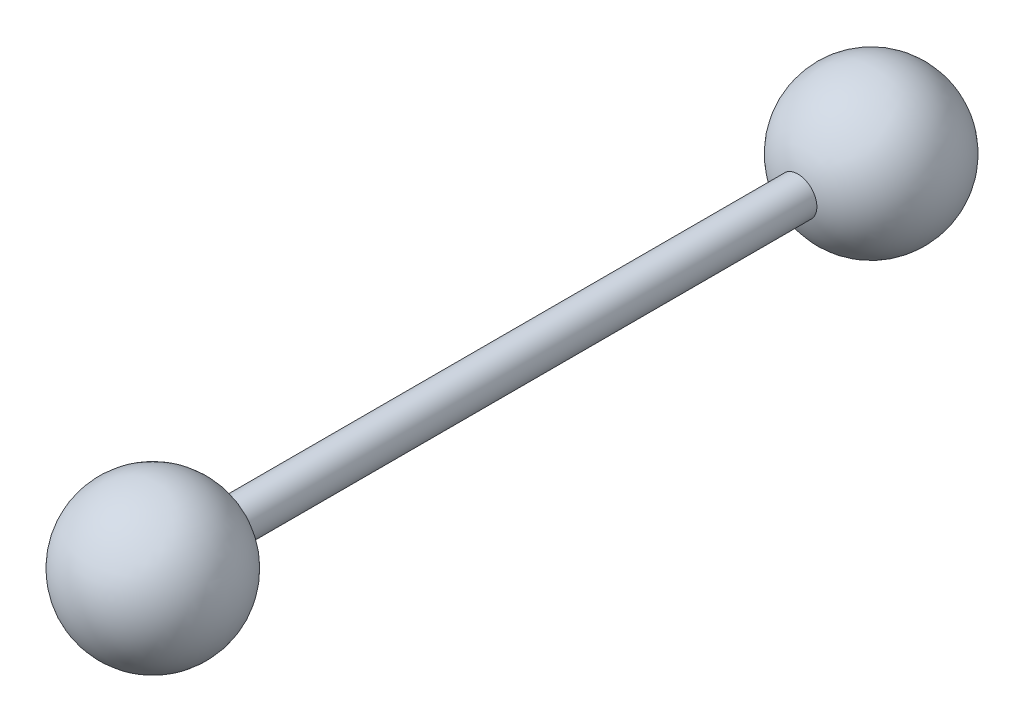
SolidWorks part; units mm, degrees
ref_plane "Front Plane" through (0, 0, 0) normal (0, 0, 1) x (1, 0, 0)
ref_plane "Top Plane" through (0, 0, 0) normal (0, 1, 0) x (1, 0, 0)
ref_plane "Right Plane" through (0, 0, 0) normal (1, 0, 0) x (0, 0, -1)
sketch "Sketch4" plane through (0, 0, 0) normal (0, 0, 1) x (1, 0, 0)
  line L0 (-3.0464, 14.6358) -> (-3.0464, -25.3642) construction
  line L1 (-3.0464, 14.6358) -> (-3.0464, 10.6358)
  line L2 (-3.0464, -25.3642) -> (-3.0464, -21.3642)
  arc A0 (-3.0464, 14.6358) -> (-3.0464, -25.3642) centre (-3.0464, -5.3642) cw
  arc A1 (-3.0464, -21.3642) -> (-3.0464, 10.6358) centre (-3.0464, -5.3642) ccw
  dimension "D4" = 16
  dimension "D5" = 20
  dimension "D1" = 40
  dimension "D2" = 4
  dimension "D3" = 4
revolve "Revolve1" add sketch "Sketch4" angle 360 about L0
ref_plane "Plane2" through (0, 0, 20) normal (0, 0, 1) x (1, 0, 0)
sketch "Sketch5" plane through (0, 0, 20) normal (0, 0, 1) x (1, 0, 0)
  circle A0 centre (-3.0464, -5.3642) radius 5
  circle A1 centre (-3.0464, -5.3642) radius 3.5
  dimension "D1" = 10
  dimension "D2" = 7
extrude "Boss-Extrude2" add sketch "Sketch5" against normal blind 4
extrude "Boss-Extrude3" add sketch "Sketch5<2>" against normal blind 4 and the other way blind 154
sketch "Sketch5<2>" plane through (0, 0, 20) normal (0, 0, 1) x (1, 0, 0) same geometry as "Sketch5"
ref_plane "Plane4" through (0, 0, 190) normal (0, 0, 1) x (1, 0, 0)
sketch "Sketch7" plane through (0, 0, 190) normal (0, 0, 1) x (1, 0, 0)
  line L0 (-3.0464, 14.6358) -> (-3.0464, -25.3642) construction
  line L1 (-3.0464, 14.6358) -> (-3.0464, 10.6358)
  line L2 (-3.0464, -25.3642) -> (-3.0464, -21.3642)
  circle A0 centre (-3.0464, -5.3642) radius 20 construction
  arc A1 (-3.0464, 10.6358) -> (-3.0464, -21.3642) centre (-3.0464, -5.3642) cw
  arc A2 (-3.0464, 14.6358) -> (-3.0464, -25.3642) centre (-3.0464, -5.3642) cw
  dimension "D1" = 4
  dimension "D2" = 4
revolve "Revolve3" add sketch "Sketch7" angle 360 about L0
